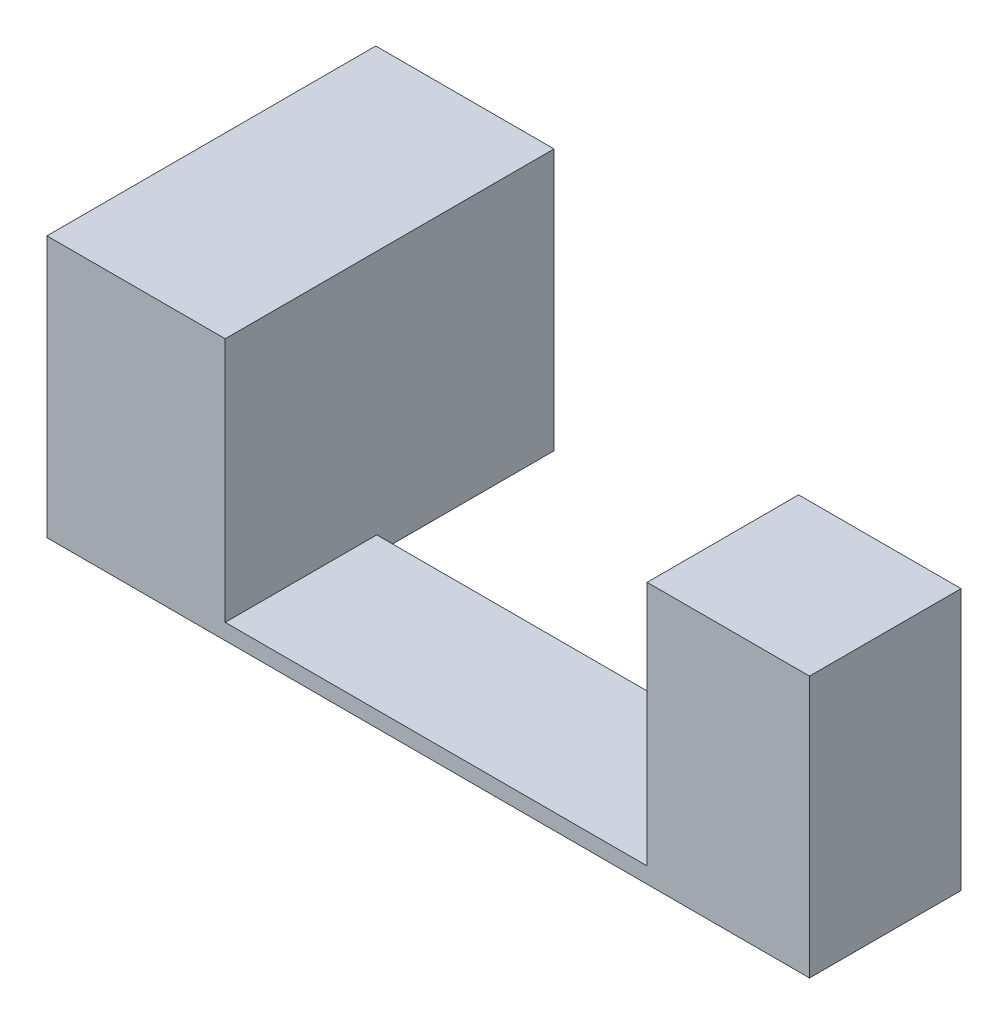
SolidWorks part; units mm, degrees
ref_plane "Piano frontale" through (0, 0, 0) normal (0, 0, 1) x (1, 0, 0)
ref_plane "Piano superiore" through (0, 0, 0) normal (0, 1, 0) x (1, 0, 0)
ref_plane "Piano destro" through (0, 0, 0) normal (1, 0, 0) x (0, 0, -1)
sketch "Schizzo1" plane through (0, 9.9972, 0) normal (0, -1, 0) x (1, 0, 0)
  line L0 (-40.686, 138.8849) -> (-21.186, 138.8849)
  line L1 (-21.861, 138.6849) -> (-6.961, 138.6849) construction
  line L2 (-40.686, 141.1579) -> (-40.686, 142.7099)
  line L3 (-40.686, 142.7099) -> (-21.186, 142.7099)
  line L4 (-21.186, 141.1579) -> (-21.186, 142.7099)
  line L5 (-25.436, 138.8849) -> (-25.436, 142.7099)
  line L6 (-36.086, 138.8849) -> (-36.086, 142.7099)
  line L7 (-21.336, 138.8849) -> (-21.336, 142.7099)
  line L8 (-40.586, 138.8849) -> (-40.586, 142.7099)
  line L9 (-36.086, 142.7099) -> (-36.086, 134.4099)
  line L11 (-21.186, 143.2099) -> (-21.186, 138.6599) construction
  line L12 (-40.686, 143.2099) -> (-40.686, 134.2099) construction
  line L13 (-19.7077, 143.2099) -> (-78.836, 143.2099) construction
  line L15 (-40.586, 138.8849) -> (-40.586, 134.4099)
  line L16 (-40.586, 134.4099) -> (-36.086, 134.4099)
  line L17 (-40.686, 134.2099) -> (-23.186, 134.2099) construction
  dimension "D1" = 4.1
  dimension "D2" = 0.15
  dimension "D3" = 4.5
  dimension "D4" = 0.1
  dimension "D5" = 0.5
  dimension "D6" = 0.2
  dimension "D7" = 0.2
extrude "Estrusione-Estrusione1" add sketch "Schizzo1" against normal up to surface (6.6 mm away) contours L8 L0 L6 L3 | L15 L16 L9 L0 | L0 L7 L3 L5 region at (-38.336, 9.9972, 140.7974) region at (-38.336, 9.9972, 136.6474) region at (-23.386, 9.9972, 140.7974)
extrude "Estrusione-Estrusione2" add sketch "Schizzo1<4>" against normal blind 0.4 contours L15 L16 L9 L0 | L8 L0 L6 L3 | L6 L0 L5 L3 | L0 L7 L3 L5 region at (-38.336, 9.9972, 140.7974) region at (-38.336, 9.9972, 136.6474) region at (-30.761, 9.9972, 140.7974) region at (-23.386, 9.9972, 140.7974)
sketch "Schizzo1<4>" plane through (0, 9.9972, 0) normal (0, -1, 0) x (1, 0, 0) same geometry as "Schizzo1"
